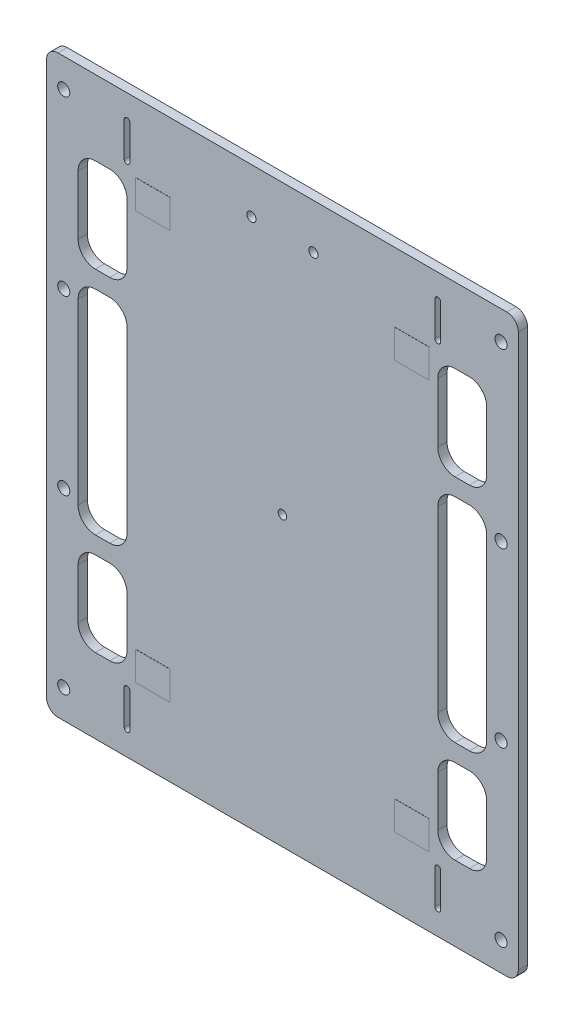
SolidWorks part; units mm, degrees
material "FR4_stuffedProtoboard"
ref_plane "Front Plane" through (0, 0, 0) normal (0, 0, 1) x (1, 0, 0)
ref_plane "Top Plane" through (0, 0, 0) normal (0, 1, 0) x (1, 0, 0)
ref_plane "Right Plane" through (0, 0, 0) normal (1, 0, 0) x (0, 0, -1)
sketch "Sketch1" plane through (0, 0, 0) normal (0, 0, 1) x (1, 0, 0)
  line L1 (-39, -50) -> (39, -50)
  line L2 (-41, -48) -> (-41, 48)
  line L3 (-39, 50) -> (39, 50)
  line L4 (41, -48) -> (41, 48)
  line L5 (-41, -50) -> (41, 50) construction
  line L6 (-41, 50) -> (41, -50) construction
  arc A0 (-39, -50) -> (-41, -48) centre (-39, -48) cw
  arc A1 (39, -50) -> (41, -48) centre (39, -48) ccw
  arc A2 (39, 50) -> (41, 48) centre (39, 48) cw
  arc A3 (-41, 48) -> (-39, 50) centre (-39, 48) cw
  point P0 (0, 0)
  dimension "D3" = 2
  dimension "D1" = 100
  dimension "D2" = 82
extrude "boardOutline" add sketch "Sketch1" along normal blind 1.6
sketch "Sketch2" plane through (0, 0, 1.6) normal (0, 0, 1) x (1, 0, 0)
  line L0 (39, 50) -> (-39, 50) construction
  line L1 (-41, 48) -> (-41, -48) construction
  line L3 (-37.5, 44.2) -> (-37.5, 4.2) construction
  circle A0 centre (0, 0) radius 0.75
  circle A1 centre (-37.5, 44.2) radius 1.05 construction
  circle A2 centre (37.5, 44.2) radius 1.05 construction
  circle A3 centre (37.5, 4.2) radius 1.05 construction
  circle A4 centre (37.5, -35.8) radius 1.05 construction
  circle A5 centre (-37.5, 4.2) radius 1.05 construction
  circle A6 centre (-37.5, -35.8) radius 1.05 construction
  circle A7 centre (-5.38, 42.15) radius 0.8
  circle A8 centre (5.39, 42.15) radius 0.8
  dimension "D1" = 1.5
  dimension "D2" = 2.1
  dimension "D9" = 10.77
  dimension "D7" = 1.6
  dimension "D11" = 7.85
  dimension "D12" = 35.62
  dimension "D3" = 5.8
  dimension "D4" = 3.5
  dimension "D8" = 40
  dimension "D10" = 37.5
  dimension "D5" = 2
  dimension "D6" = 3
extrude "componentHoles" cut sketch "Sketch2" against normal through all
sketch "Sketch4" plane through (0, 0, 1.6) normal (0, 0, 1) x (1, 0, 0)
  line L0 (-27, 39.75) -> (-27, 45.75) construction
  line L1 (-27.5, 39.75) -> (-27.5, 45.75)
  line L2 (-26.5, 39.75) -> (-26.5, 45.75)
  line L3 (39, 50) -> (-39, 50) construction
  line L4 (-41, 48) -> (-41, -48) construction
  line L5 (27, 39.75) -> (27, 45.75) construction
  line L6 (26.5, 39.75) -> (26.5, 45.75)
  line L7 (27.5, 39.75) -> (27.5, 45.75)
  line L8 (27, -45.75) -> (27, -39.75) construction
  line L9 (26.5, -45.75) -> (26.5, -39.75)
  line L10 (27.5, -45.75) -> (27.5, -39.75)
  line L11 (-27, -45.75) -> (-27, -39.75) construction
  line L12 (-27.5, -45.75) -> (-27.5, -39.75)
  line L13 (-26.5, -45.75) -> (-26.5, -39.75)
  line L14 (-27, 39.75) -> (27, 39.75) construction
  line L15 (-39, -50) -> (39, -50) construction
  arc A0 (-27.5, 39.75) -> (-26.5, 39.75) centre (-27, 39.75) ccw
  arc A1 (-26.5, 45.75) -> (-27.5, 45.75) centre (-27, 45.75) ccw
  arc A2 (26.5, 39.75) -> (27.5, 39.75) centre (27, 39.75) ccw
  arc A3 (27.5, 45.75) -> (26.5, 45.75) centre (27, 45.75) ccw
  arc A4 (26.5, -45.75) -> (27.5, -45.75) centre (27, -45.75) ccw
  arc A5 (27.5, -39.75) -> (26.5, -39.75) centre (27, -39.75) ccw
  arc A6 (-27.5, -45.75) -> (-26.5, -45.75) centre (-27, -45.75) ccw
  arc A7 (-26.5, -39.75) -> (-27.5, -39.75) centre (-27, -39.75) ccw
  point P2 (-27, 42.75)
  point P16 (27, 42.75)
  point P23 (27, -42.75)
  point P30 (-27, -42.75)
  dimension "D1" = 4.25
  dimension "D2" = 13.5
  dimension "D3" = 1
  dimension "D4" = 6
  dimension "D7" = 54
  dimension "D8" = 14
  dimension "D9" = 4.25
  dimension "D10" = 4.25
  dimension "D5" = 2
  dimension "D6" = 2
extrude "solarCellContactHoles" cut sketch "Sketch4" against normal blind 1.6
sketch "Sketch3" plane through (0, 0, 1.6) normal (0, 0, 1) x (1, 0, 0)
  line L1 (-32.5, 37) -> (-30, 37)
  line L2 (-35.5, 34) -> (-35.5, 23.7)
  line L3 (-32.5, 20.7) -> (-30, 20.7)
  line L4 (-27, 34) -> (-27, 23.7)
  line L5 (-41, 48) -> (-41, -48) construction
  line L6 (-30, -22.3) -> (-32.5, -22.3)
  line L9 (0, 50) -> (0, -50) construction
  line L10 (39, 50) -> (-39, 50) construction
  line L11 (-39, -50) -> (39, -50) construction
  line L12 (-27, -25.3) -> (-27, -34)
  line L13 (-30, -37) -> (-32.5, -37)
  line L14 (-35.5, -25.3) -> (-35.5, -34)
  line L19 (-30, -19.3) -> (-32.5, -19.3)
  line L25 (-27, -16.3) -> (-27, 14.7)
  line L26 (-30, 17.7) -> (-32.5, 17.7)
  line L27 (-35.5, -16.3) -> (-35.5, 14.7)
  arc A0 (-35.5, 23.7) -> (-32.5, 20.7) centre (-32.5, 23.7) ccw
  arc A1 (-30, 20.7) -> (-27, 23.7) centre (-30, 23.7) ccw
  arc A2 (-30, 37) -> (-27, 34) centre (-30, 34) cw
  arc A3 (-32.5, 37) -> (-35.5, 34) centre (-32.5, 34) ccw
  arc A4 (-30, -19.3) -> (-27, -16.3) centre (-30, -16.3) ccw
  arc A5 (-27, -34) -> (-30, -37) centre (-30, -34) cw
  arc A6 (-32.5, -37) -> (-35.5, -34) centre (-32.5, -34) cw
  arc A7 (-32.5, -22.3) -> (-35.5, -25.3) centre (-32.5, -25.3) ccw
  arc A8 (-30, -22.3) -> (-27, -25.3) centre (-30, -25.3) cw
  arc A17 (-32.5, -19.3) -> (-35.5, -16.3) centre (-32.5, -16.3) cw
  arc A18 (-32.5, 17.7) -> (-35.5, 14.7) centre (-32.5, 14.7) ccw
  arc A19 (-27, 14.7) -> (-30, 17.7) centre (-30, 14.7) ccw
  point P12 (-27, 20.7)
  point P15 (-27, 37)
  point P18 (-35.5, 37)
  dimension "D5" = 3
  dimension "D10" = 13
  dimension "D7" = 3
  dimension "D11" = 3
  dimension "D1" = 8.5
  dimension "D2" = 29.3
  dimension "D3" = 13
  dimension "D4" = 5.5
  dimension "D8" = 3
  dimension "D9" = 3
  dimension "D6" = 37
extrude "windows_1side" cut sketch "Sketch3" against normal through all
sketch "Sketch5" plane through (0, 0, 1.6) normal (0, 0, 1) x (1, 0, 0)
  line L0 (-41, 48) -> (-41, -48) construction
  line L1 (-25.5, 38) -> (-19.5, 38)
  line L2 (-25.5, 38) -> (-25.5, 33)
  line L3 (-25.5, 33) -> (-19.5, 33)
  line L4 (-19.5, 38) -> (-19.5, 33)
  line L5 (39, 50) -> (-39, 50) construction
  line L6 (19.5, 38) -> (19.5, 33)
  line L7 (25.5, 38) -> (25.5, 33)
  line L8 (19.5, 33) -> (25.5, 33)
  line L9 (19.5, 38) -> (25.5, 38)
  line L10 (19.5, -33) -> (19.5, -38)
  line L11 (25.5, -33) -> (25.5, -38)
  line L12 (19.5, -38) -> (25.5, -38)
  line L13 (19.5, -33) -> (25.5, -33)
  line L14 (-25.5, -33) -> (-25.5, -38)
  line L15 (-19.5, -33) -> (-19.5, -38)
  line L16 (-25.5, -38) -> (-19.5, -38)
  line L17 (-25.5, -33) -> (-19.5, -33)
  line L18 (-25.5, 38) -> (19.5, 38) construction
  line L19 (-25.5, 38) -> (-25.5, -33) construction
  dimension "D1" = 5
  dimension "D2" = 6
  dimension "D3" = 15.5
  dimension "D4" = 12
  dimension "D7" = 45
  dimension "D8" = 71
  dimension "D5" = 2
  dimension "D6" = 2
extrude "contactPads" add sketch "Sketch5" along normal blind 0.02
hole_wizard "M2 Clearance Hole1" positions "Sketch6" profile "Sketch7" hole size "M2" standard "ANSI Metric" end condition through all
sketch "Sketch6" plane through (0, 0, 0) normal (0, 0, -1) x (-1, 0, 0)
  line L5 (38, -50) -> (38, -45) construction
  line L6 (39, -50) -> (-39, -50) construction
  line L7 (38, -45) -> (38, -15) construction
  line L8 (38, -15) -> (38, 15) construction
  line L9 (38, 15) -> (38, 45) construction
  line L10 (38, 45) -> (38, 50) construction
  line L11 (-39, 50) -> (39, 50) construction
  line L14 (41, 48) -> (41, -48) construction
  point P0 (38, 45)
  point P27 (38, -15)
  point P36 (38, -45)
  point P38 (38, 15)
  dimension "D1" = 3
  dimension "D2" = 5
sketch "Sketch7" plane through (-38, 45, 0) normal (1, 0, 0) x (0, 1, 0)
  line L0 (0, 0) -> (0, 1.62)
  line L1 (0, 1.62) -> (1.05, 1.62)
  line L2 (1.05, 1.62) -> (1.05, 0)
  line L5 (1.05, 0) -> (0, 0)
  line L11 (0, -6.35) -> (0, 107.95) construction
  dimension "Thru Hole Dia." = 2.1
  dimension "Thru Hole Depth" = 1.62
mirror "Mirror1" about plane through (0, 0, 0) normal (1, 0, 0) of "M2 Clearance Hole1", "windows_1side"
sketch "Sketch8" plane through (0, 0, 1.6) normal (0, 0, 1) x (1, 0, 0)
  line L0 (-35.5, 43.5) -> (-35.5, 23.7)
  line L1 (-35.5, 14.7) -> (-35.5, -16.3)
  line L2 (-35.5, -25.3) -> (-35.5, -44)
  line L3 (-35.5, -53) -> (-35.5, -61)
  line L4 (-35.5, -70) -> (-35.5, -88.7)
  line L5 (-35.5, -97.7) -> (-35.5, -128.7)
  line L6 (-35.5, -137.7) -> (-35.5, -157.5)
  line L7 (39, 50) -> (-39, 50) construction
  line L8 (-41, 48) -> (-41, -48) construction
  line L9 (-39, -50) -> (39, -50) construction
  line L10 (41, -48) -> (41, 48) construction
  line L11 (-35.5, -25.3) -> (-35.5, -44)
  line L12 (-35.5, 14.7) -> (-35.5, -16.3)
  line L13 (-35.5, 43.5) -> (-35.5, 23.7)
  line L14 (39, 50) -> (-39, 50)
  line L15 (-41, 48) -> (-41, -48)
  line L16 (-39, -50) -> (39, -50)
  line L17 (41, -48) -> (41, 48)
  line L38 (-21, -47) -> (-32.5, -47)
  line L39 (-21, -47) -> (-32.5, -47)
  line L40 (-18, -25.3) -> (-18, -44)
  line L41 (-18, -25.3) -> (-18, -44)
  line L42 (-32.5, -22.3) -> (-21, -22.3)
  line L43 (-32.5, -22.3) -> (-21, -22.3)
  line L44 (-21, -19.3) -> (-32.5, -19.3)
  line L45 (-21, -19.3) -> (-32.5, -19.3)
  line L46 (-18, 14.7) -> (-18, -16.3)
  line L47 (-18, 14.7) -> (-18, -16.3)
  line L48 (-32.5, 17.7) -> (-21, 17.7)
  line L49 (-32.5, 17.7) -> (-21, 17.7)
  line L50 (-21, 20.7) -> (-32.5, 20.7)
  line L51 (-21, 20.7) -> (-32.5, 20.7)
  line L52 (-18, 43.5) -> (-18, 23.7)
  line L53 (-18, 43.5) -> (-18, 23.7)
  line L54 (-21, 46.5) -> (-32.5, 46.5)
  line L55 (-21, 46.5) -> (-32.5, 46.5)
  line L56 (-15, -44) -> (-15, -25.3)
  line L57 (-15, -44) -> (-15, -25.3)
  line L58 (12, -47) -> (-12, -47)
  line L59 (12, -47) -> (-12, -47)
  line L60 (15, -25.3) -> (15, -44)
  line L61 (15, -25.3) -> (15, -44)
  line L62 (-12, -22.3) -> (12, -22.3)
  line L63 (-12, -22.3) -> (12, -22.3)
  line L64 (18, -44) -> (18, -25.3)
  line L65 (18, -44) -> (18, -25.3)
  line L66 (32.5, -47) -> (21, -47)
  line L67 (32.5, -47) -> (21, -47)
  line L68 (35.5, -157.5) -> (35.5, -137.7)
  line L69 (35.5, -128.7) -> (35.5, -97.7)
  line L70 (35.5, -88.7) -> (35.5, -70)
  line L71 (35.5, -61) -> (35.5, -53)
  line L72 (35.5, -44) -> (35.5, -25.3)
  line L73 (35.5, -16.3) -> (35.5, 14.7)
  line L74 (35.5, 23.7) -> (35.5, 43.5)
  line L75 (35.5, 23.7) -> (35.5, 43.5)
  line L76 (35.5, -16.3) -> (35.5, 14.7)
  line L77 (35.5, -44) -> (35.5, -25.3)
  line L88 (32.5, 46.5) -> (21, 46.5)
  line L89 (32.5, 46.5) -> (21, 46.5)
  line L90 (18, 23.7) -> (18, 43.5)
  line L91 (18, 23.7) -> (18, 43.5)
  line L92 (32.5, 20.7) -> (21, 20.7)
  line L93 (32.5, 20.7) -> (21, 20.7)
  line L94 (21, 17.7) -> (32.5, 17.7)
  line L95 (21, 17.7) -> (32.5, 17.7)
  line L96 (18, -16.3) -> (18, 14.7)
  line L97 (18, -16.3) -> (18, 14.7)
  line L98 (32.5, -19.3) -> (21, -19.3)
  line L99 (32.5, -19.3) -> (21, -19.3)
  line L100 (21, -22.3) -> (32.5, -22.3)
  line L101 (21, -22.3) -> (32.5, -22.3)
  line L120 (-15, -16.3) -> (-15, 14.7)
  line L121 (-15, -16.3) -> (-15, 14.7)
  line L122 (12, -19.3) -> (-12, -19.3)
  line L123 (12, -19.3) -> (-12, -19.3)
  line L124 (15, 14.7) -> (15, -16.3)
  line L125 (15, 14.7) -> (15, -16.3)
  line L126 (-12, 17.7) -> (12, 17.7)
  line L127 (-12, 17.7) -> (12, 17.7)
  line L128 (-15, 23.7) -> (-15, 43.5)
  line L129 (-15, 23.7) -> (-15, 43.5)
  line L130 (12, 20.7) -> (-12, 20.7)
  line L131 (12, 20.7) -> (-12, 20.7)
  line L132 (15, 43.5) -> (15, 23.7)
  line L133 (15, 43.5) -> (15, 23.7)
  line L134 (12, 46.5) -> (-12, 46.5)
  line L135 (12, 46.5) -> (-12, 46.5)
  arc A0 (-32.5, -22.3) -> (-35.5, -25.3) centre (-32.5, -25.3) ccw
  arc A1 (-32.5, -22.3) -> (-35.5, -25.3) centre (-32.5, -25.3) ccw
  arc A2 (-39, 50) -> (-41, 48) centre (-39, 48) ccw construction
  arc A3 (-41, -48) -> (-39, -50) centre (-39, -48) ccw construction
  arc A4 (39, -50) -> (41, -48) centre (39, -48) ccw construction
  arc A5 (41, 48) -> (39, 50) centre (39, 48) ccw construction
  arc A6 (-39, 50) -> (-41, 48) centre (-39, 48) ccw
  arc A7 (-41, -48) -> (-39, -50) centre (-39, -48) ccw
  arc A8 (39, -50) -> (41, -48) centre (39, -48) ccw
  arc A9 (41, 48) -> (39, 50) centre (39, 48) ccw
  arc A34 (-35.5, -44) -> (-32.5, -47) centre (-32.5, -44) ccw
  arc A35 (-35.5, -44) -> (-32.5, -47) centre (-32.5, -44) ccw
  arc A36 (-21, -47) -> (-18, -44) centre (-21, -44) ccw
  arc A37 (-21, -47) -> (-18, -44) centre (-21, -44) ccw
  arc A38 (-18, -25.3) -> (-21, -22.3) centre (-21, -25.3) ccw
  arc A39 (-18, -25.3) -> (-21, -22.3) centre (-21, -25.3) ccw
  arc A40 (-35.5, -16.3) -> (-32.5, -19.3) centre (-32.5, -16.3) ccw
  arc A41 (-35.5, -16.3) -> (-32.5, -19.3) centre (-32.5, -16.3) ccw
  arc A42 (-21, -19.3) -> (-18, -16.3) centre (-21, -16.3) ccw
  arc A43 (-21, -19.3) -> (-18, -16.3) centre (-21, -16.3) ccw
  arc A44 (-18, 14.7) -> (-21, 17.7) centre (-21, 14.7) ccw
  arc A45 (-18, 14.7) -> (-21, 17.7) centre (-21, 14.7) ccw
  arc A46 (-32.5, 17.7) -> (-35.5, 14.7) centre (-32.5, 14.7) ccw
  arc A47 (-32.5, 17.7) -> (-35.5, 14.7) centre (-32.5, 14.7) ccw
  arc A48 (-35.5, 23.7) -> (-32.5, 20.7) centre (-32.5, 23.7) ccw
  arc A49 (-35.5, 23.7) -> (-32.5, 20.7) centre (-32.5, 23.7) ccw
  arc A50 (-21, 20.7) -> (-18, 23.7) centre (-21, 23.7) ccw
  arc A51 (-21, 20.7) -> (-18, 23.7) centre (-21, 23.7) ccw
  arc A52 (-18, 43.5) -> (-21, 46.5) centre (-21, 43.5) ccw
  arc A53 (-18, 43.5) -> (-21, 46.5) centre (-21, 43.5) ccw
  arc A54 (-32.5, 46.5) -> (-35.5, 43.5) centre (-32.5, 43.5) ccw
  arc A55 (-32.5, 46.5) -> (-35.5, 43.5) centre (-32.5, 43.5) ccw
  arc A56 (-12, -22.3) -> (-15, -25.3) centre (-12, -25.3) ccw
  arc A57 (-12, -22.3) -> (-15, -25.3) centre (-12, -25.3) ccw
  arc A58 (-15, -44) -> (-12, -47) centre (-12, -44) ccw
  arc A59 (-15, -44) -> (-12, -47) centre (-12, -44) ccw
  arc A60 (12, -47) -> (15, -44) centre (12, -44) ccw
  arc A61 (12, -47) -> (15, -44) centre (12, -44) ccw
  arc A62 (15, -25.3) -> (12, -22.3) centre (12, -25.3) ccw
  arc A63 (15, -25.3) -> (12, -22.3) centre (12, -25.3) ccw
  arc A64 (21, -22.3) -> (18, -25.3) centre (21, -25.3) ccw
  arc A65 (21, -22.3) -> (18, -25.3) centre (21, -25.3) ccw
  arc A66 (18, -44) -> (21, -47) centre (21, -44) ccw
  arc A67 (18, -44) -> (21, -47) centre (21, -44) ccw
  arc A68 (32.5, -47) -> (35.5, -44) centre (32.5, -44) ccw
  arc A69 (32.5, -47) -> (35.5, -44) centre (32.5, -44) ccw
  arc A78 (35.5, 43.5) -> (32.5, 46.5) centre (32.5, 43.5) ccw
  arc A79 (35.5, 43.5) -> (32.5, 46.5) centre (32.5, 43.5) ccw
  arc A80 (21, 46.5) -> (18, 43.5) centre (21, 43.5) ccw
  arc A81 (21, 46.5) -> (18, 43.5) centre (21, 43.5) ccw
  arc A82 (18, 23.7) -> (21, 20.7) centre (21, 23.7) ccw
  arc A83 (18, 23.7) -> (21, 20.7) centre (21, 23.7) ccw
  arc A84 (32.5, 20.7) -> (35.5, 23.7) centre (32.5, 23.7) ccw
  arc A85 (32.5, 20.7) -> (35.5, 23.7) centre (32.5, 23.7) ccw
  arc A86 (35.5, 14.7) -> (32.5, 17.7) centre (32.5, 14.7) ccw
  arc A87 (35.5, 14.7) -> (32.5, 17.7) centre (32.5, 14.7) ccw
  arc A88 (21, 17.7) -> (18, 14.7) centre (21, 14.7) ccw
  arc A89 (21, 17.7) -> (18, 14.7) centre (21, 14.7) ccw
  arc A90 (18, -16.3) -> (21, -19.3) centre (21, -16.3) ccw
  arc A91 (18, -16.3) -> (21, -19.3) centre (21, -16.3) ccw
  arc A92 (32.5, -19.3) -> (35.5, -16.3) centre (32.5, -16.3) ccw
  arc A93 (32.5, -19.3) -> (35.5, -16.3) centre (32.5, -16.3) ccw
  arc A94 (35.5, -25.3) -> (32.5, -22.3) centre (32.5, -25.3) ccw
  arc A95 (35.5, -25.3) -> (32.5, -22.3) centre (32.5, -25.3) ccw
  arc A120 (-12, 17.7) -> (-15, 14.7) centre (-12, 14.7) ccw
  arc A121 (-12, 17.7) -> (-15, 14.7) centre (-12, 14.7) ccw
  arc A122 (-15, -16.3) -> (-12, -19.3) centre (-12, -16.3) ccw
  arc A123 (-15, -16.3) -> (-12, -19.3) centre (-12, -16.3) ccw
  arc A124 (12, -19.3) -> (15, -16.3) centre (12, -16.3) ccw
  arc A125 (12, -19.3) -> (15, -16.3) centre (12, -16.3) ccw
  arc A126 (15, 14.7) -> (12, 17.7) centre (12, 14.7) ccw
  arc A127 (15, 14.7) -> (12, 17.7) centre (12, 14.7) ccw
  arc A128 (-12, 46.5) -> (-15, 43.5) centre (-12, 43.5) ccw
  arc A129 (-12, 46.5) -> (-15, 43.5) centre (-12, 43.5) ccw
  arc A130 (-15, 23.7) -> (-12, 20.7) centre (-12, 23.7) ccw
  arc A131 (-15, 23.7) -> (-12, 20.7) centre (-12, 23.7) ccw
  arc A132 (12, 20.7) -> (15, 23.7) centre (12, 23.7) ccw
  arc A133 (12, 20.7) -> (15, 23.7) centre (12, 23.7) ccw
  arc A134 (15, 43.5) -> (12, 46.5) centre (12, 43.5) ccw
  arc A135 (15, 43.5) -> (12, 46.5) centre (12, 43.5) ccw
